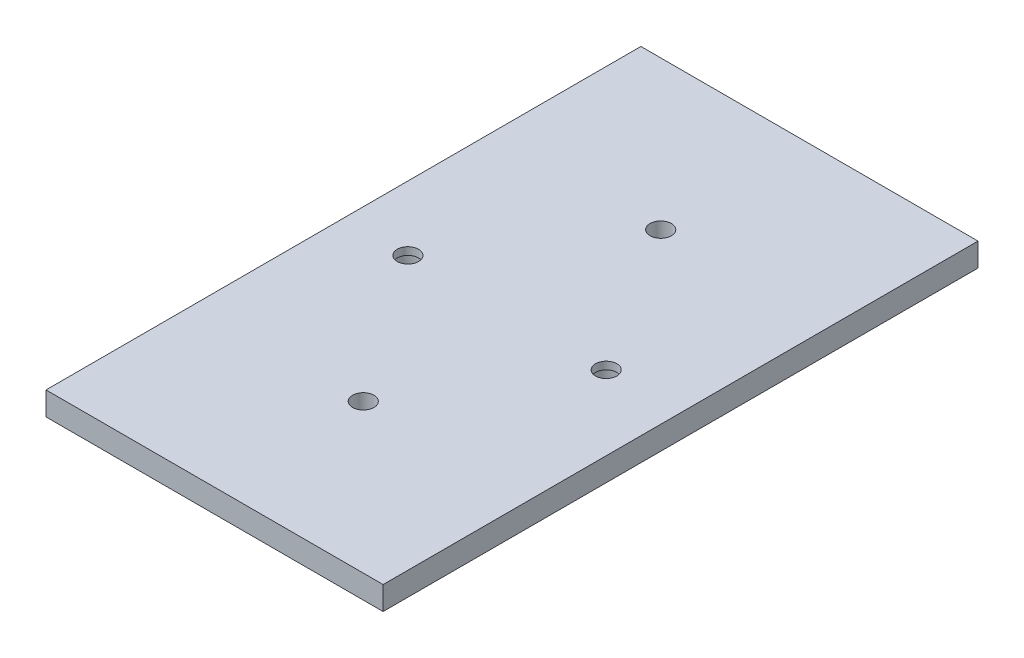
SolidWorks part; units mm, degrees
ref_plane "Front Plane" through (0, 0, 0) normal (0, 0, 1) x (1, 0, 0)
ref_plane "Top Plane" through (0, 0, 0) normal (0, 1, 0) x (1, 0, 0)
ref_plane "Right Plane" through (0, 0, 0) normal (1, 0, 0) x (0, 0, -1)
sketch "Sketch2" plane through (0, 0, 0) normal (0, 1, 0) x (1, 0, 0)
  line L2 (0, 0) -> (0, 152.4)
  line L4 (88.9, 0) -> (88.9, 152.4)
  line L10 (-1000, 76.2) -> (49000, 76.2) construction
  line L13 (0, 152.4) -> (88.9, 152.4)
  line L14 (0, 0) -> (88.9, 0)
  point P11 (0, 76.2)
  dimension "D1" = 152.4
  dimension "D2" = 88.9
extrude "Boss-Extrude1" add sketch "Sketch2" along normal blind 5.9944 contours L4 L13 L2 L14
sketch "Sketch4" plane through (0, 5.9944, 0) normal (0, 1, 0) x (1, 0, 0)
  line L0 (0, 0) -> (0, 152.4) construction
  line L2 (45.72, 114.3) -> (45.72, 38.1) construction
  line L3 (0, 0) -> (0, 152.4) construction
  circle A0 centre (45.72, 114.3) radius 2.7305
  circle A1 centre (45.72, 38.1) radius 2.7305
  point P4 (45.72, 76.2)
  point P6 (0, 0)
  point P10 (0, 76.2)
  dimension "D3" = 5.461
  dimension "D4" = 5.461
  dimension "D1" = 76.2
  dimension "D2" = 45.72
extrude "Cut-Extrude2" cut sketch "Sketch4" against normal through all both
sketch "Sketch5" plane through (0, 5.9944, 0) normal (0, 1, 0) x (1, 0, 0)
  line L6 (88.9, 0) -> (88.9, 152.4) construction
  line L7 (19.05, 76.2) -> (69.85, 76.2) construction
  line L8 (0, 152.4) -> (88.9, 152.4) construction
  circle A0 centre (69.85, 76.2) radius 2.7305
  circle A1 centre (19.05, 76.2) radius 2.7305
  point P6 (44.45, 152.4)
  point P9 (88.9, 76.2)
  point P10 (44.45, 76.2)
  dimension "D1" = 5.461
  dimension "D2" = 5.461
  dimension "D3" = 50.8
extrude "Cut-Extrude3" cut sketch "Sketch5" against normal through all both and the other way through all
sketch "Sketch7" plane through (0, 5.9944, 0) normal (0, 1, 0) x (1, 0, 0)
  line L0 (0, 0) -> (88.9, 0) construction
  line L1 (0, 152.4) -> (2.54, 152.4)
  line L2 (0, 152.4) -> (0, 0)
  line L3 (0, 0) -> (2.54, 0)
  line L4 (2.54, 152.4) -> (2.54, 0)
  dimension "D1" = 2.54
extrude "Cut-Extrude5" cut sketch "Sketch7" against normal through all both and the other way through all
sketch "Sketch8" plane through (0, 0, 0) normal (0, -1, 0) x (1, 0, 0)
  circle A0 centre (19.05, -76.2) radius 3.683
  circle A2 centre (69.85, -76.2) radius 3.683
  dimension "D1" = 7.366
  dimension "D2" = 7.366
extrude "Cut-Extrude6" cut sketch "Sketch8" against normal blind 4.064
equation "\"threaded_insert_hole\"=0.1472"
equation "\"th\"=1.25249"
